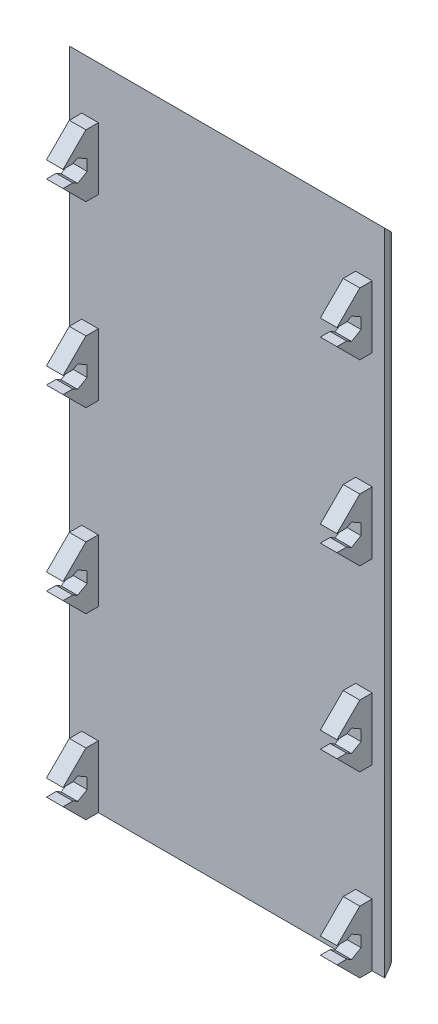
SolidWorks part; units mm, degrees
ref_plane "Front Plane" through (0, 0, 0) normal (0, 0, 1) x (1, 0, 0)
ref_plane "Top Plane" through (0, 0, 0) normal (0, 1, 0) x (1, 0, 0)
ref_plane "Right Plane" through (0, 0, 0) normal (1, 0, 0) x (0, 0, -1)
sketch "Sketch1" plane through (0, 0, 0) normal (0, 1, 0) x (1, 0, 0)
  line L0 (-9.2151, 0) -> (-9.2151, -10)
  line L1 (-9.2151, -10) -> (-5.2151, -10)
  line L2 (-5.2151, -10) -> (-5.2151, 0)
  line L3 (-5.2151, 0) -> (56.7849, 0)
  line L4 (56.7849, 0) -> (56.7849, -10)
  line L5 (56.7849, -10) -> (60.7849, -10)
  line L6 (60.7849, -10) -> (60.7849, 0)
  line L7 (60.7849, 0) -> (63.7849, 0)
  line L8 (-9.2151, 0) -> (-12.2151, 0)
  line L9 (-12.2151, 0) -> (-8.1737, 7)
  line L10 (-8.1737, 7) -> (59.7434, 7)
  line L11 (59.7434, 7) -> (63.7849, 0)
  line L12 (25.7849, 7) -> (25.7849, 0) construction
  dimension "D1" = 3
  dimension "D2" = 10
  dimension "D3" = 70
  dimension "D4" = 7
  dimension "D5" = 4
  dimension "D6" = 60
extrude "Boss-Extrude1" add sketch "Sketch1" along normal blind 156.5
sketch "Sketch4" plane through (60.7849, 0, 0) normal (1, 0, 0) x (0, 0, -1)
  line L0 (0, 156.5) -> (0, 0) construction
  line L1 (-37.5185, 156.5) -> (0, 156.5)
  line L2 (-37.5185, 156.5) -> (-37.5185, 144)
  line L3 (-37.5185, 144) -> (0, 144)
  line L4 (0, 156.5) -> (0, 144)
  line L5 (-37.5185, 156.5) -> (0, 144) construction
  line L6 (-37.5185, 144) -> (0, 156.5) construction
  line L7 (-10, 156.5) -> (0, 156.5) construction
  point P0 (-18.7592, 150.25)
  dimension "D1" = 12.5
extrude "Cut-Extrude1" cut sketch "Sketch4" against normal through all
sketch "Sketch5" plane through (60.7849, 0, 0) normal (1, 0, 0) x (0, 0, -1)
  line L0 (0, 156.5) -> (0, 0) construction
  line L1 (-33.3149, 129) -> (0, 129)
  line L2 (-33.3149, 129) -> (-33.3149, 101)
  line L3 (-33.3149, 101) -> (0, 101)
  line L4 (0, 129) -> (0, 101)
  line L5 (-33.3149, 129) -> (0, 101) construction
  line L6 (-33.3149, 101) -> (0, 129) construction
  line L7 (-10, 144) -> (0, 144) construction
  point P0 (-16.6574, 115)
  dimension "D1" = 28
  dimension "D2" = 15
extrude "Cut-Extrude2" cut sketch "Sketch5" against normal through all
sketch "Sketch6" plane through (0, 0, 0) normal (1, 0, 0) x (0, 0, -1)
  line L0 (-10, 144) -> (-10, 129) construction
  line L1 (-2.7, 137.8279) -> (-5, 139.1558)
  line L2 (-5, 139.1558) -> (-7.3, 137.8279)
  line L3 (-7.3, 137.8279) -> (-7.3, 135.1721)
  line L4 (-7.3, 135.1721) -> (-5, 133.8442)
  line L5 (-5, 133.8442) -> (-2.7, 135.1721)
  line L6 (-2.7, 135.1721) -> (-2.7, 137.8279)
  line L7 (-10, 144) -> (0, 144) construction
  line L8 (-6.15, 138.4919) -> (-10, 138.4919)
  line L9 (-6.15, 134.5081) -> (-10, 134.5081)
  line L10 (-10, 134.5081) -> (-10, 138.4919)
  circle A1 centre (-5, 136.5) radius 2.3 construction
  dimension "D1" = 4.6
  dimension "D2" = 7.5
  dimension "D3" = 5
extrude "Cut-Extrude3" cut sketch "Sketch6" against normal through all and the other way through all contours L10 L9 L4 L3 L2 L8 | L5 L6 L1 L2 L3 L4 region at (0, 136.5, 5) region at (0, 136.5, 8.5351)
pattern_linear "LPattern1" count 4 spacing 43 along (0, -1, 0) of "Cut-Extrude2", "Cut-Extrude3"
chamfer "Chamfer3" distance 7 angle 45 1 edges at (25.7849, 156.5, -7)
fillet "Fillet1" radius 8 2 edges at (-8.1737, 74.75, -7) (59.7434, 74.75, -7)
chamfer "Chamfer5" distance 7 angle 45 16 edges at (58.7849, 43, 10) (58.7849, 144, 10) (58.7849, 129, 10) (-7.2151, 144, 10) (-7.2151, 129, 10) (-7.2151, 101, 10) (-7.2151, 86, 10) (58.7849, 101, 10) (58.7849, 86, 10) (58.7849, 58, 10) (58.7849, 0, 10) (58.7849, 15, 10) (-7.2151, 0, 10) (-7.2151, 15, 10) (-7.2151, 58, 10) (-7.2151, 43, 10)
sketch "Sketch7" plane through (0, 0, -7) normal (0, 0, -1) x (-1, 0, 0)
  line L8 (3.5549, 51.8135) -> (-11.316, 51.8135) construction
  line L14 (-11.316, 97.6865) -> (-40.2538, 97.6865) construction
  line L20 (-11.316, 97.6865) -> (-11.316, 51.8135) construction
  line L22 (-40.2538, 97.6865) -> (-40.2538, 51.8135) construction
  line L23 (-11.316, 51.8135) -> (-40.2538, 51.8135) construction
  line L24 (3.5549, 0) -> (3.5549, 149.5) construction
  line L25 (-11.316, 96.6865) -> (-11.316, 85.2639)
  line L26 (-12.316, 97.6865) -> (-39.2538, 97.6865)
  line L27 (-11.316, 84.6865) -> (-40.2538, 84.6865) construction
  line L28 (-40.2538, 96.6865) -> (-40.2538, 84.6865)
  line L29 (-40.2538, 51.8135) -> (-55.1246, 51.8135) construction
  line L30 (-55.1246, 149.5) -> (-55.1246, 0) construction
  line L31 (-11.316, 149.5) -> (-11.316, 97.6865) construction
  line L32 (3.5549, 149.5) -> (-55.1246, 149.5) construction
  line L33 (-11.316, 51.8135) -> (-11.316, 0) construction
  line L34 (-55.1246, 0) -> (3.5549, 0) construction
  line L35 (-11.316, 76.6036) -> (-17.816, 72.8509)
  line L38 (-25.316, 68.5207) -> (-39.7538, 60.185)
  line L39 (-11.316, 76.6036) -> (-11.316, 62.3135)
  line L40 (-40.2538, 59.319) -> (-40.2538, 51.8135)
  line L41 (-40.2538, 51.8135) -> (-32.316, 56.3964)
  line L42 (-32.316, 56.3964) -> (-32.316, 62.3135) construction
  line L43 (-18.316, 71.9848) -> (-18.316, 62.3135)
  line L44 (-11.316, 62.3135) -> (-32.316, 62.3135) construction
  line L45 (-25.316, 68.5207) -> (-25.316, 62.3135)
  line L46 (-18.316, 62.3135) -> (-25.316, 62.3135) construction
  line L47 (-39.7538, 76.3509) -> (-18.566, 88.5836)
  line L48 (-40.2538, 84.6865) -> (-40.2538, 76.0622) construction
  line L49 (-11.316, 51.8135) -> (-40.2538, 51.8135) construction
  line L50 (-40.2538, 75.4848) -> (-40.2538, 69.6395)
  line L51 (-32.316, 56.3964) -> (-30.9714, 57.1727)
  line L52 (-11.816, 84.3979) -> (-31.566, 72.9952)
  line L53 (-33.2538, 90.1865) -> (-33.2538, 88.4752)
  line L54 (-31.566, 72.1292) -> (-25.316, 68.5207)
  line L55 (-32.316, 64.4793) -> (-39.7538, 68.7735)
  line L56 (-33.5038, 88.0422) -> (-40.2538, 84.1451)
  line L57 (-40.2538, 84.1451) -> (-40.2538, 84.6865)
  line L58 (-32.7538, 90.6865) -> (-18.816, 90.6865)
  line L59 (-18.316, 90.1865) -> (-18.316, 89.0167)
  line L60 (-11.316, 90.6865) -> (-18.316, 90.6865) construction
  line L61 (-33.2538, 90.6865) -> (-40.2538, 90.6865) construction
  line L62 (-40.2538, 97.6865) -> (-11.316, 97.6865) construction
  line L63 (-11.316, 97.6865) -> (-11.316, 51.8135) construction
  arc A7 (-11.316, 62.3135) -> (-32.316, 62.3135) centre (-21.816, 62.3135) cw
  arc A8 (-18.316, 62.3135) -> (-25.316, 62.3135) centre (-21.816, 62.3135) cw
  arc A9 (-17.816, 72.8509) -> (-18.316, 71.9848) centre (-17.316, 71.9848) ccw
  arc A10 (-11.816, 84.3979) -> (-11.316, 85.2639) centre (-12.316, 85.2639) ccw
  arc A11 (-11.316, 96.6865) -> (-12.316, 97.6865) centre (-12.316, 96.6865) ccw
  arc A12 (-39.7538, 60.185) -> (-40.2538, 59.319) centre (-39.2538, 59.319) ccw
  arc A13 (-39.2538, 97.6865) -> (-40.2538, 96.6865) centre (-39.2538, 96.6865) ccw
  arc A14 (-40.2538, 75.4848) -> (-39.7538, 76.3509) centre (-39.2538, 75.4848) cw
  arc A15 (-39.7538, 68.7735) -> (-40.2538, 69.6395) centre (-39.2538, 69.6395) cw
  arc A16 (-32.7538, 90.6865) -> (-33.2538, 90.1865) centre (-32.7538, 90.1865) ccw
  arc A17 (-33.5038, 88.0422) -> (-33.2538, 88.4752) centre (-33.7538, 88.4752) ccw
  arc A18 (-18.316, 90.1865) -> (-18.816, 90.6865) centre (-18.816, 90.1865) ccw
  arc A19 (-18.566, 88.5836) -> (-18.316, 89.0167) centre (-18.816, 89.0167) ccw
  arc A20 (-31.566, 72.1292) -> (-31.566, 72.9952) centre (-31.316, 72.5622) cw
  point P59 (-40.2538, 76.0622)
  point P63 (-40.2538, 69.0622)
  dimension "D11" = 7
  dimension "D12" = 30
  dimension "D10" = 7
  dimension "D14" = 0.5
  dimension "D16" = 7
  dimension "D6" = 7
  dimension "D13" = 1
  dimension "D2" = 1
  dimension "0.5" = 1
  dimension "D18" = 1
  dimension "D4" = 0.5
  dimension "D1" = 7
  dimension "D3" = 7
  dimension "D5" = 7
  dimension "D7" = 7
  dimension "D8" = 7
  dimension "D9" = 7
  dimension "D15" = 30
  dimension "D17" = 7
extrude "Cut-Extrude4" cut sketch "Sketch7" against normal blind 1 contours L54 A20 L52 A10 L25 A11 L26 A13 L28 L57 L56 L53 L58 L59 L47 A14 L50 A15 L55 L38 | L38 A12 L40 L41 L51 A7 L39 L35 A9 L43 A8 L45 region at (11.7564, 90.9752, -7) region at (25.697, 65.4171, -7)
fillet "Fillet2" radius 0.5 2 edges at (32.316, 64.4793, -6.5) (25.316, 68.5207, -6.5)
